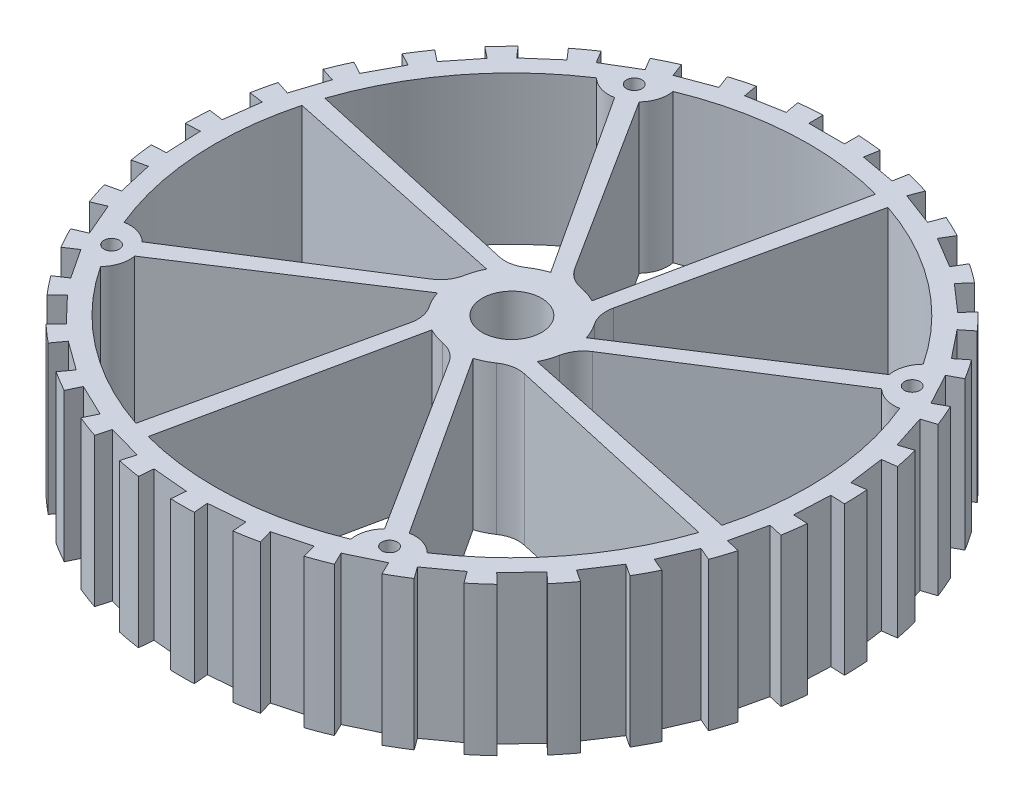
SolidWorks part; units mm, degrees
material "Magnesium Alloy"
ref_plane "Front Plane" through (0, 0, 0) normal (0, 0, 1) x (1, 0, 0)
ref_plane "Top Plane" through (0, 0, 0) normal (0, 1, 0) x (1, 0, 0)
ref_plane "Right Plane" through (0, 0, 0) normal (1, 0, 0) x (0, 0, -1)
sketch "Sketch6" plane through (0, 0, 0) normal (0, 0, 1) x (1, 0, 0)
  line L0 (55, 0) -> (-55, 0) construction
  line L1 (6.35, 15.875) -> (70.485, 15.875)
  line L2 (6.35, 15.875) -> (6.35, -15.875)
  line L3 (6.35, -15.875) -> (70.485, -15.875)
  line L4 (70.485, 15.875) -> (70.485, -15.875)
  line L5 (0, -55) -> (0, 55) construction
  line L6 (0, 36.96) -> (0, -27.3202) construction
  dimension "D1" = 15.875
  dimension "D2" = 15.875
  dimension "D3" = 70.485
  dimension "D4" = 6.35
revolve "Revolve1" add sketch "Sketch6" angle 360 about L6
sketch "Sketch7" plane through (0, 15.875, 0) normal (0, 1, 0) x (1, 0, 0)
  line L0 (20.2102, 60.198) -> (8.8135, 9.144)
  line L1 (12.115, 3.81) -> (54.9926, 31.75)
  line L2 (-55, 0) -> (55, 0) construction
  arc A0 (12.115, 3.81) -> (8.8135, 9.144) centre (0, 0) ccw
  arc A1 (54.9926, 31.75) -> (20.2102, 60.198) centre (0, 0) ccw
  dimension "D1" = 12.7
  dimension "D2" = 63.5
  dimension "D3" = 31.75
  dimension "D4" = 3.81
  dimension "D5" = 60.198
extrude "Cut-Extrude4" cut sketch "Sketch7" against normal blind 31.75
pattern_circular "CirPattern1" count 8 over 360 about axis through (0, 36.96, 0) along (0, 1, 0) of "Cut-Extrude4" reverse direction yes
sketch "Sketch9" plane through (0, 0, 0) normal (0, 1, 0) x (1, 0, 0)
  line L0 (-17.4625, 0) -> (17.4625, 0) construction
  line L1 (-3.81, 72.9107) -> (3.81, 72.9107)
  line L2 (-3.81, 72.9107) -> (-3.81, 67.31)
  line L3 (-3.81, 67.31) -> (3.81, 67.31)
  line L4 (3.81, 72.9107) -> (3.81, 67.31)
  line L5 (0, -17.4625) -> (0, 17.4625) construction
  dimension "D1" = 7.62
  dimension "D2" = 67.31
  dimension "D3" = 3.81
extrude "Cut-Extrude5" cut sketch "Sketch9" against normal mid plane 31.75
pattern_circular "CirPattern2" count 35 over 360 about axis through (0, 36.96, 0) along (0, 1, 0) of "Cut-Extrude5" reverse direction yes
sketch "Sketch10" plane through (0, 0, 0) normal (0, 1, 0) x (1, 0, 0)
  line L0 (-17.4625, 0) -> (17.4625, 0) construction
  line L1 (-2.54, 8.89) -> (2.54, 8.89)
  line L2 (-2.54, 8.89) -> (-2.54, 2.54)
  line L3 (-2.54, 2.54) -> (2.54, 2.54)
  line L4 (2.54, 8.89) -> (2.54, 2.54)
  line L5 (0, -17.4625) -> (0, 17.4625) construction
  dimension "D1" = 2.54
  dimension "D2" = 8.89
  dimension "D3" = 2.54
  dimension "D4" = 5.08
extrude "Cut-Extrude6" [suppressed] cut sketch "Sketch10" against normal mid plane 31.75
fillet "Fillet1" radius 6.35 8 edges at (-0.2337, 0, -12.6978) (12.6978, 0, -0.2337) (8.8135, 0, -9.144) (9.144, 0, 8.8135) (0.2337, 0, 12.6978) (-9.144, 0, -8.8135) (-8.8135, 0, 9.144) (-12.6978, 0, 0.2337)
sketch "Sketch11" plane through (0, 15.875, 0) normal (0, 1, 0) x (1, 0, 0)
  line L0 (-36.195, 54.7892) -> (-24.765, 60.325)
  line L1 (0, -17.4625) -> (0, 17.4625) construction
  line L2 (-17.4625, 0) -> (17.4625, 0) construction
  arc A0 (-24.765, 60.325) -> (-36.195, 54.7892) centre (-30.48, 57.5571) cw
  dimension "D1" = 6.35
  dimension "D2" = 24.765
  dimension "D3" = 60.325
  dimension "D4" = 36.195
extrude "Boss-Extrude1" add sketch "Sketch11" against normal blind 31.75
pattern_circular "CirPattern3" count 4 over 360 about axis through (0, 36.96, 0) along (0, 1, 0) of "Boss-Extrude1" reverse direction yes
sketch "Sketch12" plane through (0, 15.875, 0) normal (0, 1, 0) x (1, 0, 0)
  line L0 (0, -17.4625) -> (0, 17.4625) construction
  line L1 (-17.4625, 0) -> (17.4625, 0) construction
  circle A0 centre (-29.718, 55.88) radius 1.651
  dimension "D2" = 3.302
  dimension "D3" = 55.88
  dimension "D1" = 29.718
extrude "Cut-Extrude7" cut sketch "Sketch12" against normal blind 31.75
pattern_circular "CirPattern4" count 4 over 360 about axis through (0, 36.96, 0) along (0, 1, 0) of "Cut-Extrude7" reverse direction yes
ref_axis "Axis1" through (-29.718, -15.875, -55.88) along (0, 1, 0)
ref_axis "Axis2" through (0, -15.875, 0) along (0, 1, 0)
